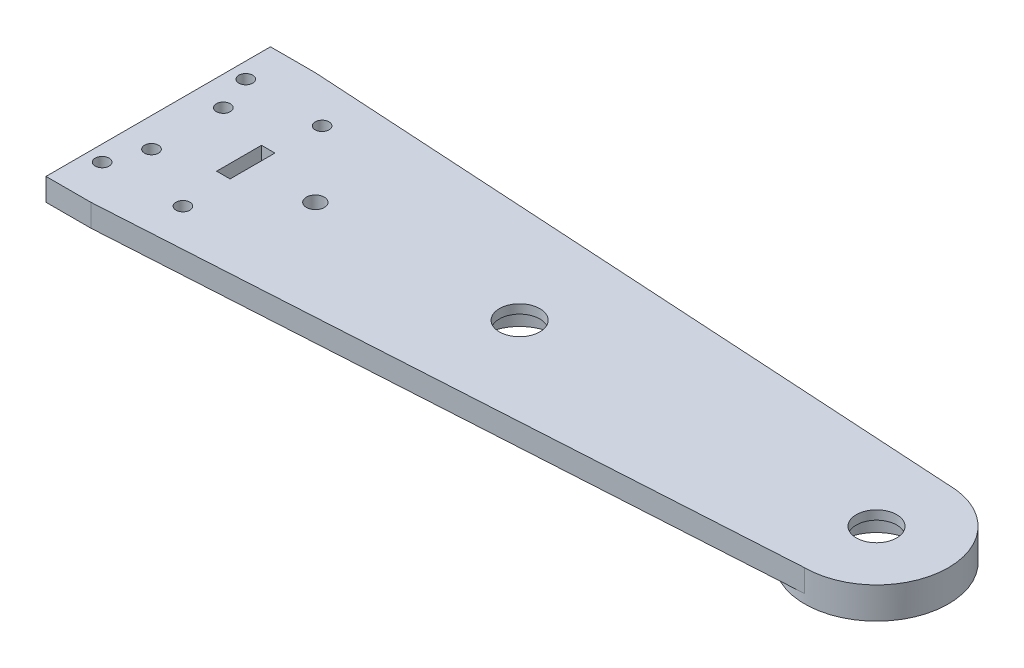
SolidWorks part; units mm, degrees
ref_plane "Front Plane" through (0, 0, 0) normal (0, 0, 1) x (1, 0, 0)
ref_plane "Top Plane" through (0, 0, 0) normal (0, 1, 0) x (1, 0, 0)
ref_plane "Right Plane" through (0, 0, 0) normal (1, 0, 0) x (0, 0, -1)
sketch "Sketch28" plane through (-32, 0, 0) normal (0, -1, 0) x (0, 0, 1)
  line L1 (0, -20) -> (0, -65.5) construction
  line L2 (-8, 8.5) -> (8, 8.5) construction
  line L3 (0, 15) -> (0, -3) construction
  line L8 (-25, 15) -> (25, 15)
  line L12 (25, 15) -> (25, 5)
  line L13 (-25, 15) -> (-25, 5)
  line L14 (-25, 5) -> (-16, -145)
  line L15 (16, -145) -> (25, 5)
  line L16 (-25, 5) -> (-25, 8.5) construction
  line L17 (-25, 8.5) -> (-8, 8.5) construction
  line L18 (-25, 15) -> (-25, 11.5) construction
  line L19 (-25, 11.5) -> (-16, 11.5) construction
  line L20 (-16, 11.5) -> (16, 11.5) construction
  line L21 (-5, -3) -> (5, -3)
  line L26 (5, -3) -> (5, -6)
  line L27 (5, -6) -> (-5, -6)
  line L28 (-5, -6) -> (-5, -3)
  line L29 (-5, -3) -> (-15.5, -3) construction
  line L30 (-15.5, -3) -> (-15.5, -6) construction
  line L31 (5, -3) -> (15.5, -3) construction
  line L32 (15.5, -3) -> (15.5, -6) construction
  line L33 (0, -20) -> (0, -6) construction
  line L34 (0, -65.5) -> (0, -145) construction
  circle A7 centre (8, 8.5) radius 1.55
  circle A8 centre (-8, 8.5) radius 1.55
  circle A9 centre (16, 11.5) radius 1.55
  circle A10 centre (-16, 11.5) radius 1.55
  circle A13 centre (-15.5, -6) radius 1.55
  circle A14 centre (15.5, -6) radius 1.55
  circle A15 centre (0, -20) radius 12.5 construction
  circle A19 centre (0, -65.5) radius 4.5
  circle A20 centre (0, -20) radius 2
  circle A21 centre (0, -145) radius 4.5
  arc A22 (-16, -145) -> (16, -145) centre (0, -145) ccw
  point P13 (0, 15)
  point P27 (0, -3)
  point P40 (0, 0)
extrude "Boss-Extrude10" add sketch "Sketch28" along normal blind 5
sketch "Sketch29" plane through (0, -5, 0) normal (0, -1, 0) x (1, 0, 0)
  circle A0 centre (33.5, 0) radius 16
  circle A5 centre (113, 0) radius 16
extrude "Boss-Extrude11" add sketch "Sketch29" along normal blind 2
sketch "Sketch30" plane through (0, -7, 0) normal (0, -1, 0) x (1, 0, 0)
  circle A0 centre (33.5, 0) radius 8.2
  circle A1 centre (113, 0) radius 8.2
extrude "Cut-Extrude1" cut sketch "Sketch30" against normal blind 5
